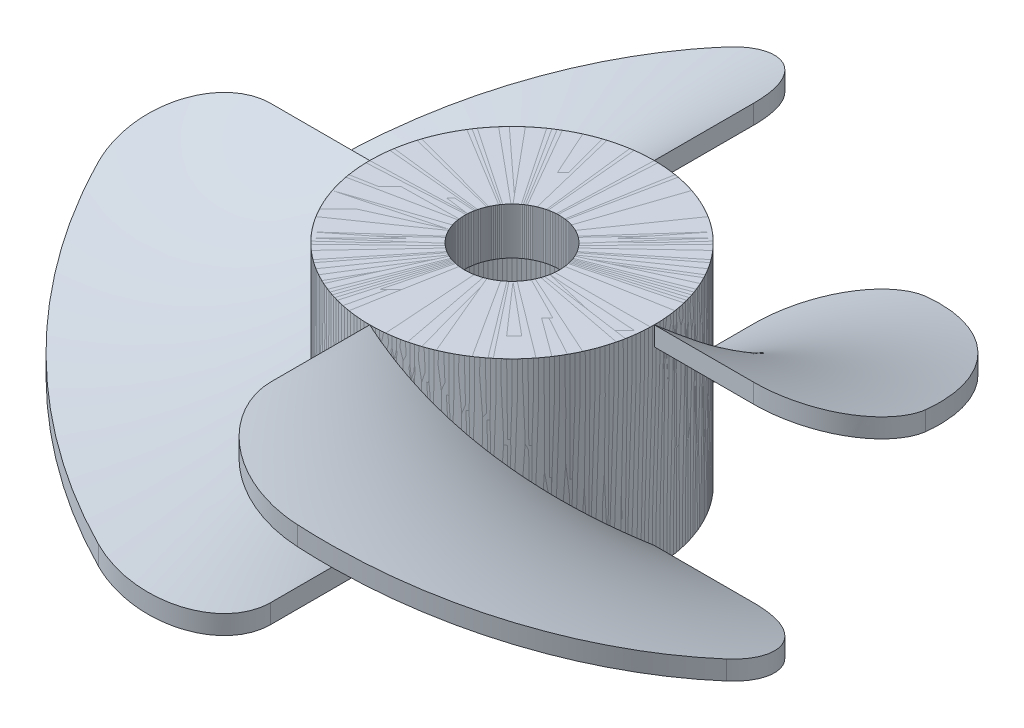
SolidWorks part; units mm, degrees
ref_plane "Front Plane" through (0, 0, 0) normal (0, 0, 1) x (1, 0, 0)
ref_plane "Top Plane" through (0, 0, 0) normal (0, 1, 0) x (1, 0, 0)
ref_plane "Right Plane" through (0, 0, 0) normal (1, 0, 0) x (0, 0, -1)
sketch "Sketch3" plane through (0, 0, 0) normal (0, 1, 0) x (1, 0, 0)
  circle A0 centre (0, 0) radius 14.9
  dimension "D1" = 14.9
curve "Helix/Spiral3" pitch 80 height 20 radius 14.9 left hand yes centre (0, 0, 0) axis (0, 1, 0) start towards (0, 0, 1)
sketch "Sketch10" plane through (0, 0, 0) normal (0, 0, 1) x (1, 0, 0)
  line L0 (-14.9, 0) -> (0, 0) construction
  line L1 (-34.5, 1) -> (-14.9, 1)
  line L2 (-34.5, 1) -> (-34.5, -1)
  line L3 (-34.5, -1) -> (-14.9, -1)
  line L4 (-14.9, 1) -> (-14.9, -1)
  line L5 (-34.5, 1) -> (-14.9, -1) construction
  line L6 (-34.5, -1) -> (-14.9, 1) construction
  spline S1 degree 3 poles (-14.9, 0) (-14.9, 1.6605) (-14.1244, 5.0026) (-10.8093, 10) (-5.8537, 14.9974) (-1.9432, 18.3395) (0, 20) knots 0 0 0 0 0.25 0.5 0.75 1 1 1 1 construction
  point P0 (-24.7, 0)
  dimension "D1" = 2
  dimension "D2" = 19.6
sweep "Sweep2" add profiles "Sketch10" path "Helix/Spiral3"
sketch "Sketch13" plane through (0, 0, 0) normal (0, 1, 0) x (1, 0, 0)
  circle A0 centre (0, 0) radius 14.9
  circle A1 centre (0, 0) radius 12
  circle A2 centre (0, 0) radius 4.965
  dimension "D1" = 12
  dimension "D2" = 4.965
extrude "Boss-Extrude1" add sketch "Sketch13" along normal blind 21 and the other way blind 1 contours A2 | A1 A2 | A0 A1 region at (-14.4786, 0, 0) region at (-11.6606, 0, 0) region at (0, 0, 0)
fillet "Fillet6" radius 8 2 edges at (-34.5, 0, 0)
extrude "Cut-Extrude1" cut sketch "Sketch13<3>" against normal blind 16.1 and the other way blind 16.1 contours A1 A2 | A2 region at (-11.6606, 0, 0) region at (0, 0, 0)
sketch "Sketch13<3>" plane through (0, 0, 0) normal (0, 1, 0) x (1, 0, 0) same geometry as "Sketch13"
extrude "Cut-Extrude3" cut sketch "Sketch13<4>" along normal blind 1000 and the other way blind 16.1 contours A2 region at (0, 0, 0)
sketch "Sketch13<4>" plane through (0, 0, 0) normal (0, 1, 0) x (1, 0, 0) same geometry as "Sketch13"
pattern_circular "CirPattern1" count 4 over 360 about axis through (0, -1, 0) along (0, 1, 0) reverse direction yes of bodies 105
